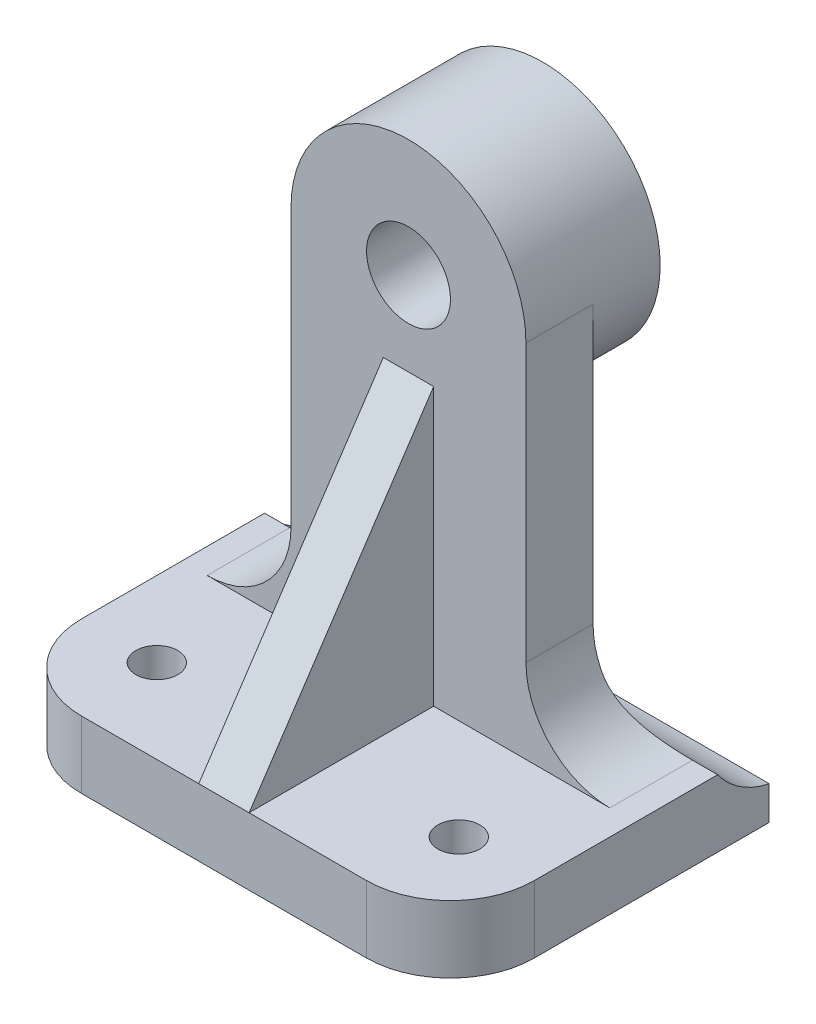
SolidWorks part; units mm, degrees
ref_plane "Ön Düzlem" through (0, 0, 0) normal (0, 0, 1) x (1, 0, 0)
ref_plane "Üst Düzlem" through (0, 0, 0) normal (0, 1, 0) x (1, 0, 0)
ref_plane "Sağ Düzlem" through (0, 0, 0) normal (1, 0, 0) x (0, 0, -1)
sketch "Çizim1" plane through (0, 0, 0) normal (1, 0, 0) x (0, 0, -1)
  line L1 (-6.9167, 9.8333) -> (-36.9167, 9.8333)
  line L2 (-6.9167, 9.8333) -> (-6.9167, 5.8333)
  line L3 (-19.3333, 1.8333) -> (-36.9167, 1.8333)
  line L4 (-36.9167, 9.8333) -> (-36.9167, 1.8333)
  line L5 (-6.9167, 5.8333) -> (1.0833, 5.8333)
  line L7 (-19.3333, 1.8333) -> (1.0833, 1.8333)
  line L8 (1.0833, 5.8333) -> (1.0833, 1.8333)
  dimension "D1" = 8
  dimension "D2" = 4
  dimension "D3" = 38
  dimension "D4" = 8
extrude "Yükseklik-Ekstrüzyon1" add sketch "Çizim1" along normal blind 54
sketch "Çizim2" plane through (0, 0, 6.9167) normal (0, 0, -1) x (-1, 0, 0)
  line L0 (-41, 52.8333) -> (-41, 9.8333)
  line L1 (-13, 52.8333) -> (-13, 9.8333)
  line L2 (-54, 9.8333) -> (0, 9.8333) construction
  arc A0 (-13, 52.8333) -> (-41, 52.8333) centre (-27, 52.8333) ccw
  circle A1 centre (-27, 52.8333) radius 5
  line M4 (0, 9.8333) -> (-54, 9.8333)
  dimension "D1" = 28
  dimension "D2" = 10
  dimension "D3" = 43
  dimension "D4" = 27
extrude "Yükseklik-Ekstrüzyon2" add sketch "Çizim2" against normal blind 8 contours L1 A0 L0 A1 M4 region at (27, 36.0496, 6.9167)
ref_plane "Düzlem1" through (27, 0, 0) normal (1, 0, 0) x (0, 0, -1)
sketch "Çizim6" plane through (27, 0, 0) normal (1, 0, 0) x (0, 0, -1)
  line L0 (-36.9167, 9.8333) -> (-14.9167, 42.8333)
  line L1 (-14.9167, 52.8333) -> (-14.9167, 9.8333) construction
  dimension "D1" = 33
rib "Feder2" sketch "Çizim6" sketch "Çizim6" thickness 6 extrusion direction parallel to sketch draft on no parameters "D1"=6
sketch "Çizim7" plane through (0, 0, 6.9167) normal (0, 0, -1) x (-1, 0, 0)
  circle A0 centre (-27, 52.8333) radius 5
  circle A1 centre (-27, 52.8333) radius 14
extrude "Yükseklik-Ekstrüzyon3" add sketch "Çizim7" along normal blind 8
fillet "Radyus1" radius 10 2 edges at (41, 9.8333, 10.9167) (13, 9.8333, 10.9167)
fillet "Radyus2" radius 10 1 edges at (27, 5.8333, 6.9167)
fillet "Radyus3" radius 10 2 edges at (0, 5.8333, 36.9167) (54, 5.8333, 36.9167)
sketch "Çizim9" plane through (0, 9.8333, 0) normal (0, 1, 0) x (1, 0, 0)
  line L0 (24, -36.9167) -> (10, -36.9167) construction
  line L1 (0, -5.0643) -> (0, -26.9167) construction
  line L2 (54, -5.0643) -> (54, -26.9167) construction
  circle A0 centre (9, -26.9167) radius 2.5
  circle A1 centre (45, -26.9167) radius 2.5
  point P7 (0, 0)
  dimension "D2" = 5
  dimension "D3" = 5
  dimension "D1" = 10
  dimension "D4" = 36
  dimension "D5" = 9
  dimension "D6" = 9
extrude "Kes-Ekstrüzyon1" cut sketch "Çizim9" against normal through all
